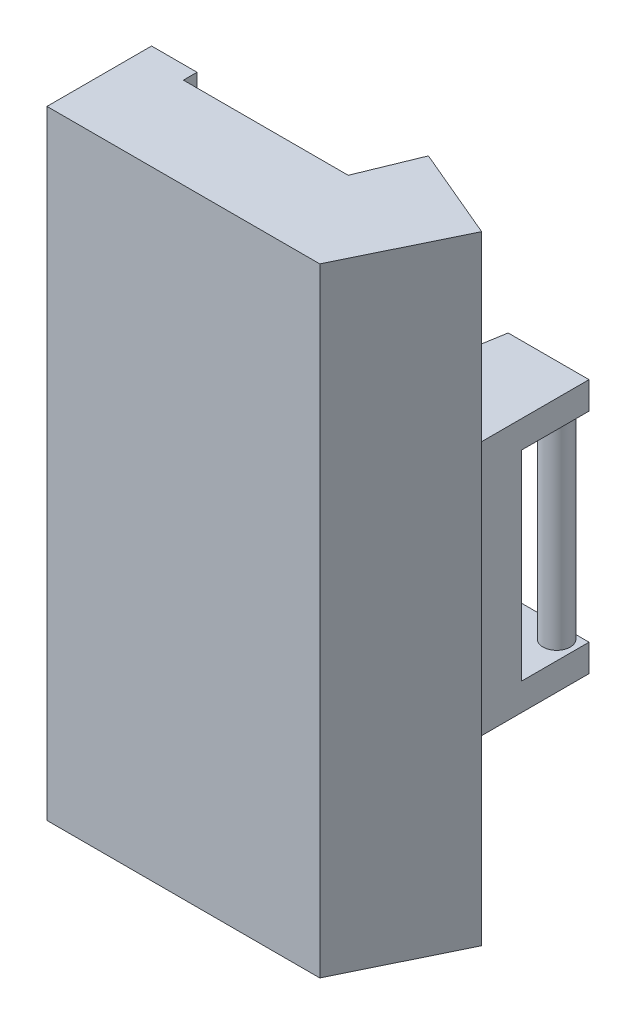
SolidWorks part; units mm, degrees
ref_plane "Plan de face" through (0, 0, 0) normal (0, 0, 1) x (1, 0, 0)
ref_plane "Plan de dessus" through (0, 0, 0) normal (0, 1, 0) x (1, 0, 0)
ref_plane "Plan de droite" through (0, 0, 0) normal (1, 0, 0) x (0, 0, -1)
sketch "Esquisse1" plane through (0, 0, 0) normal (0, 1, 0) x (1, 0, 0)
  circle A0 centre (0, 0) radius 1.5
extrude "Boss.-Extru.1" add sketch "Esquisse1" along normal blind 11 and the other way blind 11
sketch "Esquisse2" plane through (0, -11, 0) normal (0, -1, 0) x (1, 0, 0)
  line L4 (2.0617, 10.309) -> (-3.7596, 22.2799)
  line L5 (-3.7596, 22.2799) -> (-33.7596, 22.2799)
  line L6 (-33.7596, 22.2799) -> (-33.7596, 12.2799)
  line L7 (-33.7596, 12.2799) -> (-28.7596, 12.2799)
  line L8 (-28.7596, 12.2799) -> (-28.7596, 10.2799)
  line L9 (-28.7596, 10.2799) -> (-23.7596, 10.2799)
  line L10 (-23.7596, 10.2799) -> (-23.7596, 12.2799)
  line L12 (-10.6354, 12.2799) -> (-23.7596, 12.2799)
  line L15 (-8.0759, 6.0212) -> (2.0617, 5.9045)
  line L16 (2.0617, 5.9045) -> (2.0617, 10.309)
  line L17 (-8.0759, 6.0212) -> (-10.6354, 12.2799)
extrude "Boss.-Extru.3" add sketch "Esquisse2" against normal blind 25 and the other way blind 3 separate body
sketch "Esquisse3" plane through (0, -11, 0) normal (0, -1, 0) x (1, 0, 0)
  line L0 (0, -1.5) -> (-6.8319, -1.5)
  line L1 (-6.8319, -1.5) -> (-8.0759, 6.0212)
  line L2 (-8.0759, 6.0212) -> (2.0617, 5.9045)
  line L3 (2.0617, 5.9045) -> (2.0617, -1.5)
  line L4 (2.0617, -1.5) -> (0, -1.5)
  circle A0 centre (0, 0) radius 1.5 construction
extrude "Boss.-Extru.4" add sketch "Esquisse3" along normal blind 3
sketch "Esquisse4" plane through (0, 11, 0) normal (0, 1, 0) x (1, 0, 0)
  line L0 (2.0617, 1.5) -> (-6.8319, 1.5)
  line L1 (-6.8319, 1.5) -> (-8.0759, -6.0212)
  line L2 (-8.0759, -6.0212) -> (2.0617, -5.9045)
  line L3 (2.0617, -5.9045) -> (2.0617, 1.5)
extrude "Boss.-Extru.5" add sketch "Esquisse4" along normal blind 3
sketch "Esquisse5" plane through (0, 14, 0) normal (0, 1, 0) x (1, 0, 0)
  line L0 (-23.7596, -12.2799) -> (-28.7596, -12.2799)
  line L1 (-28.7596, -12.2799) -> (-28.7596, -10.2799)
  line L2 (-28.7596, -10.2799) -> (-23.7596, -10.2799)
  line L3 (-23.7596, -10.2799) -> (-23.7596, -12.2799)
extrude "Enlèv. mat.-Extru.1" cut sketch "Esquisse5" against normal blind 39
sketch "Esquisse6" plane through (0, 14, 0) normal (0, 1, 0) x (1, 0, 0)
  line L0 (-33.7596, -12.2799) -> (-33.7596, -10.7799)
  line L1 (-33.7596, -10.7799) -> (-28.7596, -10.7799)
  line L2 (-28.7596, -10.7799) -> (-28.7596, -12.2799)
  line L3 (-33.7596, -12.2799) -> (-10.6354, -12.2799) construction
  line L4 (-33.7596, -12.2799) -> (-28.7596, -12.2799)
extrude "Boss.-Extru.6" add sketch "Esquisse6" against normal up to surface (28 mm away) up to face at (-11.5873, -14, 10.3062)
sketch "Esquisse7" plane through (0, -14, 0) normal (0, -1, 0) x (1, 0, 0)
  line L0 (2.0617, 10.309) -> (-8.0759, 6.0212)
  line L1 (-8.0759, 6.0212) -> (-10.6354, 12.2799)
  line L2 (-10.6354, 12.2799) -> (-28.7596, 12.2799)
  line L3 (-28.7596, 12.2799) -> (-28.7596, 10.7799)
  line L4 (-28.7596, 10.7799) -> (-33.7596, 10.7799)
  line L5 (-33.7596, 10.7799) -> (-33.7596, 22.2799)
  line L6 (-33.7596, 22.2799) -> (-3.7596, 22.2799)
  line L7 (-3.7596, 22.2799) -> (2.0617, 10.309)
extrude "Boss.-Extru.7" add sketch "Esquisse7" along normal blind 20 and the other way blind 48
